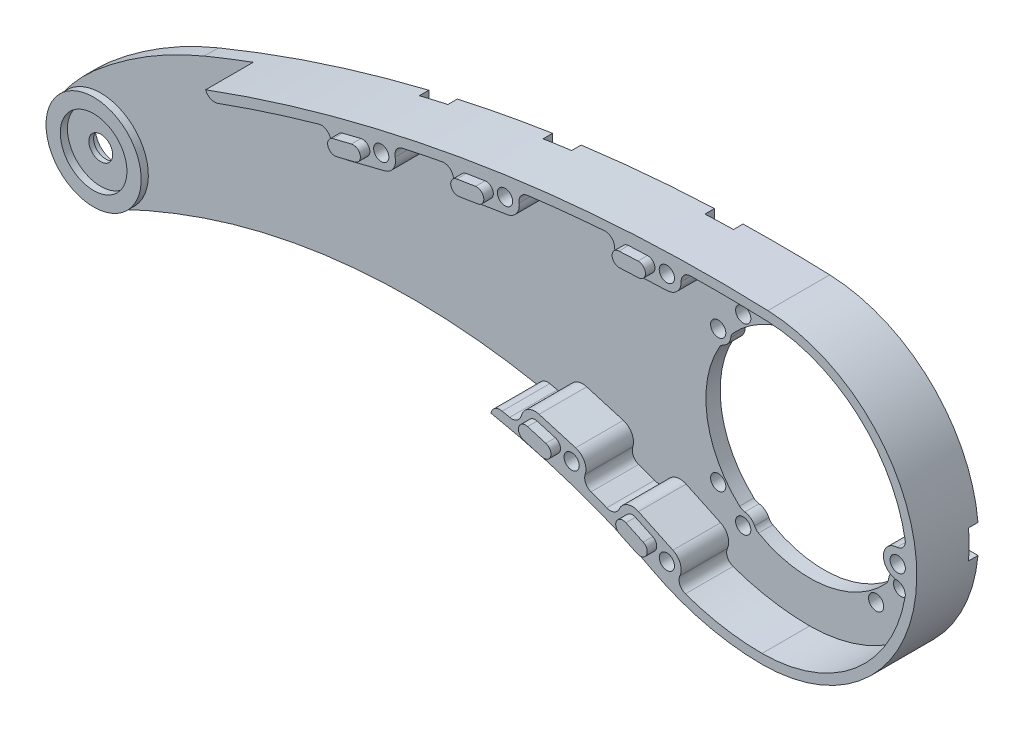
SolidWorks part; units mm, degrees
material "6061-T6 (SS)"
ref_plane "前视基准面" through (0, 0, 0) normal (0, 0, 1) x (1, 0, 0)
ref_plane "上视基准面" through (0, 0, 0) normal (0, 1, 0) x (1, 0, 0)
ref_plane "右视基准面" through (0, 0, 0) normal (1, 0, 0) x (0, 0, -1)
other "Configuration Table"
sketch "草图1" plane through (0, 0, 0) normal (0, 0, 1) x (1, 0, 0)
  line L0 (-74.3846, 0) -> (17.4339, 0) construction
  line L1 (0, 31.8895) -> (0, -25.7876) construction
  line L2 (0, 0) -> (19.2142, 13.9599) construction
  line L3 (0, 0) -> (13.9599, 19.2142) construction
  line L4 (0, 0) -> (-148.9161, -18) construction
  line L6 (0, 0) -> (-1.2281, 22.9672) construction
  line L8 (-1.2281, 22.9672) -> (-150.1441, 4.9672) construction
  line L9 (-150.1441, 4.9672) -> (-148.9161, -18) construction
  line L10 (-148.9161, -18) -> (-97.5528, -158.9319)
  line L12 (0, 0) -> (-103.1063, -167.9797) construction
  arc A116 (16.0762, 14.724) -> (-10.7394, 18.9712) centre (0, 0) ccw
  circle A117 centre (0, 0) radius 23.75 construction
  circle A118 centre (19.2142, 13.9599) radius 1.6
  circle A119 centre (13.9599, 19.2142) radius 1.6
  circle A120 centre (19.2142, -13.9599) radius 1.6
  circle A121 centre (13.9599, -19.2142) radius 1.6
  circle A122 centre (-13.9599, -19.2142) radius 1.6
  circle A123 centre (-19.2142, -13.9599) radius 1.6
  circle A124 centre (-19.2142, 13.9599) radius 1.6
  circle A125 centre (-13.9599, 19.2142) radius 1.6
  arc A126 (0, -32.5) -> (1.2171, 32.4772) centre (0, 0) ccw
  arc A127 (-157.1671, -12.3502) -> (-144.5702, -27.0063) centre (-148.9161, -18) ccw
  arc A134 (-28.3708, -24.2609) -> (-127.3793, -19.9637) centre (-83.3912, -149.2082) ccw
  arc A135 (-127.3793, -19.9637) -> (-144.5702, -27.0063) centre (-78.0965, -164.7651) ccw
  arc A136 (1.2171, 32.4772) -> (-127.1723, 9.5805) centre (-10.2849, -274.4361) ccw
  arc A138 (-23.6381, -26.5665) -> (-28.3708, -24.2609) centre (-55.9067, -86.7929) ccw
  arc A139 (0, -32.5) -> (-23.6381, -26.5665) centre (0, 17.5518) cw
  arc A140 (16.5853, 13.6255) -> (18.0838, 11.5631) centre (19.2142, 13.9599) ccw
  arc A141 (16.5853, 13.6255) -> (16.0762, 14.724) centre (14.6013, 13.3732) ccw
  arc A142 (18.0838, 11.5631) -> (18.9712, 10.7394) centre (17.2307, 9.7541) cw
  arc A143 (11.5631, -18.0838) -> (10.7394, -18.9712) centre (9.7541, -17.2307) cw
  arc A144 (13.6255, -16.5853) -> (11.5631, -18.0838) centre (13.9599, -19.2142) ccw
  arc A145 (13.6255, -16.5853) -> (14.724, -16.0762) centre (13.3732, -14.6013) ccw
  arc A146 (-18.0838, -11.5631) -> (-18.9712, -10.7394) centre (-17.2307, -9.7541) cw
  arc A147 (-16.5853, -13.6255) -> (-18.0838, -11.5631) centre (-19.2142, -13.9599) ccw
  arc A148 (-16.5853, -13.6255) -> (-16.0762, -14.724) centre (-14.6013, -13.3732) ccw
  arc A149 (-11.5631, 18.0838) -> (-10.7394, 18.9712) centre (-9.7541, 17.2307) cw
  arc A150 (-13.6255, 16.5853) -> (-11.5631, 18.0838) centre (-13.9599, 19.2142) ccw
  arc A151 (-13.6255, 16.5853) -> (-14.724, 16.0762) centre (-13.3732, 14.6013) ccw
  arc A152 (-16.0762, -14.724) -> (10.7394, -18.9712) centre (0, 0) ccw
  arc A153 (14.724, -16.0762) -> (18.9712, 10.7394) centre (0, 0) ccw
  arc A154 (-14.724, 16.0762) -> (-18.9712, -10.7394) centre (0, 0) ccw
  arc A155 (-127.1723, 9.5805) -> (-150.1438, -4.5112) centre (-94.9478, -68.7195) ccw
  arc A156 (-150.1438, -4.5112) -> (-157.1671, -12.3502) centre (-123.7132, -35.2574) ccw
  arc A157 (11.5631, 18.0838) -> (10.7394, 18.9712) centre (9.7541, 17.2307) ccw
  arc A158 (11.5631, 18.0838) -> (13.6255, 16.5853) centre (13.9599, 19.2142) ccw
  arc A159 (13.6255, 16.5853) -> (14.724, 16.0762) centre (13.3732, 14.6013) cw
  arc A160 (16.5853, -13.6255) -> (16.0762, -14.724) centre (14.6013, -13.3732) cw
  arc A161 (18.0838, -11.5631) -> (16.5853, -13.6255) centre (19.2142, -13.9599) ccw
  arc A162 (18.0838, -11.5631) -> (18.9712, -10.7394) centre (17.2307, -9.7541) ccw
  arc A163 (-13.6255, -16.5853) -> (-14.724, -16.0762) centre (-13.3732, -14.6013) cw
  arc A164 (-11.5631, -18.0838) -> (-13.6255, -16.5853) centre (-13.9599, -19.2142) ccw
  arc A165 (-11.5631, -18.0838) -> (-10.7394, -18.9712) centre (-9.7541, -17.2307) ccw
  arc A166 (-16.5853, 13.6255) -> (-16.0762, 14.724) centre (-14.6013, 13.3732) cw
  arc A167 (-18.0838, 11.5631) -> (-16.5853, 13.6255) centre (-19.2142, 13.9599) ccw
  arc A168 (-18.0838, 11.5631) -> (-18.9712, 10.7394) centre (-17.2307, 9.7541) ccw
  arc A169 (18.9712, 10.7394) -> (16.0762, 14.724) centre (0, 0) ccw
  arc A170 (-10.7394, 18.9712) -> (-14.724, 16.0762) centre (0, 0) ccw
  arc A171 (10.7394, -18.9712) -> (14.724, -16.0762) centre (0, 0) ccw
  arc A172 (-16.0762, -14.724) -> (-18.9712, -10.7394) centre (0, 0) cw
  point P27 (0, 0)
  point P73 (0, 0)
  point P83 (0, 0)
  point P105 (0, 0)
  dimension "D1" = 43.6
  dimension "D3" = 36
  dimension "D4" = 3.2
  dimension "D2" = 47.5
  dimension "D6" = 3.2
  dimension "D8" = 65
  dimension "D15" = 20
  dimension "D16" = 5.3
  dimension "D17" = 2
  dimension "D5" = 18
  dimension "D9" = 18
  dimension "D10" = 150
  dimension "D11" = 23
  dimension "D12" = 150
  dimension "D13" = 103.132
  dimension "D14" = 51.566
  dimension "D19" = 2
  dimension "D7" = 4
  dimension "D18" = 4
  dimension "D20" = 4
extrude "凸台-拉伸1" add sketch "草图1" along normal blind 3 contours A135 A134 A138 A126 A127 A125 A124 A123 A122 A121 A120 A119 A118 A116 | A168 A167 A166 A154 | A158 A159 A116 A157 | A162 A161 A160 A153 | A165 A164 A163 A152 region at (12.6444, 17.4035, 0) region at (17.4035, -12.6444, 0) region at (-17.4035, 12.6444, 0) region at (-12.6444, -17.4035, 0) region at (-60.0806, 1.6127, 0)
sketch "草图2" plane through (0, 0, 0) normal (0, 0, -1) x (-1, 0, 0)
  line L0 (-28.5, 0) -> (0, 0) construction
  line L2 (0, 0) -> (18.5599, 13.5842) construction
  line L3 (18.5599, 13.5842) -> (167.476, -4.4158) construction
  line L4 (167.476, -4.4158) -> (148.9161, -18) construction
  line L5 (148.9161, -18) -> (10.6983, -76.2738) construction
  line L7 (25.351, 15.2815) -> (162.3611, -1.2794) construction
  line L9 (24.751, 10.3176) -> (161.7611, -6.2433) construction
  line L11 (19.8643, 25.54) -> (27.8561, 25.1781)
  line L13 (18.7235, -21.0787) -> (25.9631, -17.6745)
  line L16 (53.5282, 22.5613) -> (61.4287, 21.3032)
  line L17 (79.2716, 17.6568) -> (87.0322, 15.7143)
  line L19 (116.7753, -9.6208) -> (124.5035, -11.6883)
  line L20 (39.1553, -12.6715) -> (46.8316, -10.4188)
  arc A111 (-1.1422, 30.4786) -> (-30.0624, 5.1483) centre (0, 0) ccw
  arc A112 (0, -30.5) -> (16.1065, -27.7202) centre (0, 17.5518) ccw
  arc A114 (110.6875, -13.3991) -> (53.0075, -14.0564) centre (83.3912, -149.2082) ccw
  arc A115 (128.6525, -18.2859) -> (127.8763, -18.0203) centre (78.0965, -164.7651) ccw
  arc A116 (144.5702, -27.0063) -> (157.1671, -12.3502) centre (148.9161, -18) ccw
  arc A118 (157.1671, -12.3502) -> (150.1438, -4.5112) centre (123.7132, -35.2574) ccw
  arc A119 (127.1723, 9.5805) -> (-1.2171, 32.4772) centre (10.2849, -274.4361) ccw
  arc A120 (-1.2171, 32.4772) -> (0, -32.5) centre (0, 0) ccw
  arc A121 (-1.0673, 28.48) -> (0, -28.5) centre (0, 0) ccw construction
  arc A122 (0, -32.5) -> (23.6381, -26.5665) centre (0, 17.5518) ccw
  arc A123 (28.3708, -24.2609) -> (23.6381, -26.5665) centre (55.9067, -86.7929) ccw
  arc A124 (127.3793, -19.9637) -> (28.3708, -24.2609) centre (83.3912, -149.2082) ccw
  arc A125 (144.5702, -27.0063) -> (127.3793, -19.9637) centre (78.0965, -164.7651) ccw
  arc A126 (144.5702, -27.0063) -> (157.1671, -12.3502) centre (148.9161, -18) ccw
  arc A128 (127.1723, 9.5805) -> (-1.2171, 32.4772) centre (10.2849, -274.4361) ccw
  arc A129 (-1.2171, 32.4772) -> (0, -32.5) centre (0, 0) ccw
  arc A130 (0, -32.5) -> (23.6381, -26.5665) centre (0, 17.5518) ccw
  arc A131 (28.3708, -24.2609) -> (23.6381, -26.5665) centre (55.9067, -86.7929) ccw
  arc A132 (127.3793, -19.9637) -> (28.3708, -24.2609) centre (83.3912, -149.2082) ccw
  arc A133 (144.5702, -27.0063) -> (127.3793, -19.9637) centre (78.0965, -164.7651) ccw
  arc A134 (0, -28.5) -> (21.749, -23.0407) centre (0, 17.5518) ccw construction
  arc A135 (26.7587, -20.6001) -> (21.749, -23.0407) centre (55.9067, -86.7929) ccw construction
  arc A136 (128.6681, -16.177) -> (26.7587, -20.6001) centre (83.3912, -149.2082) ccw construction
  arc A137 (146.3086, -23.4038) -> (128.6681, -16.177) centre (78.0965, -164.7651) ccw construction
  arc A138 (146.3086, -23.4038) -> (153.7238, -14.4104) centre (148.9161, -18) ccw construction
  arc A139 (153.7238, -14.4104) -> (126.0955, 5.6977) centre (120.8678, -30.5198) ccw construction
  arc A140 (126.0955, 5.6977) -> (-1.0673, 28.48) centre (10.2849, -274.4361) ccw construction
  arc A141 (-28.3421, -2.9958) -> (-28.3421, 2.9958) centre (-28.5, 0) ccw
  arc A142 (-28.3421, 2.9958) -> (-30.0624, 5.1483) centre (-28.2451, 4.837) cw
  arc A143 (-28.3421, -2.9958) -> (-30.0624, -5.1483) centre (-28.2451, -4.837) ccw
  arc A144 (-30.0624, -5.1483) -> (0, -30.5) centre (0, 0) ccw
  circle A145 centre (-28.5, 0) radius 1.6
  arc A146 (-1.1422, 30.4786) -> (0, -30.5) centre (0, 0) ccw construction
  circle A147 centre (18.5599, 13.5842) radius 7 construction
  circle A148 centre (167.476, -4.4158) radius 6 construction
  arc A149 (17.0011, 28.6182) -> (19.8643, 25.54) centre (20, 28.5369) ccw
  arc A150 (27.8561, 25.1781) -> (30.9858, 27.985) centre (27.9918, 28.175) ccw
  arc A151 (17.0011, 28.6182) -> (15.0491, 30.6555) centre (15.0181, 28.672) ccw
  arc A152 (30.9858, 27.985) -> (33.1139, 29.8374) centre (32.9655, 27.8593) cw
  arc A153 (15.0491, 30.6555) -> (-1.1422, 30.4786) centre (10.2849, -274.4361) ccw
  circle A154 centre (20, 28.5369) radius 1.6
  arc A155 (126.6313, 7.6402) -> (-1.1422, 30.4786) centre (10.2849, -274.4361) ccw construction
  arc A156 (17.2617, -25.019) -> (18.7235, -21.0787) centre (20, -23.7935) cw
  arc A157 (25.9631, -17.6745) -> (30.0023, -19.2201) centre (27.2396, -20.3894) cw
  circle A158 centre (20, -23.7935) radius 1.6
  arc A159 (17.2617, -25.019) -> (16.1065, -27.7202) centre (15.4362, -25.8359) cw
  arc A160 (30.0023, -19.2201) -> (32.6241, -20.3211) centre (31.8778, -18.4263) ccw
  circle A161 centre (54, 25.524) radius 1.6
  arc A162 (27.5648, -22.4305) -> (22.6935, -24.8036) centre (55.9067, -86.7929) ccw construction
  arc A163 (0, -30.5) -> (22.6935, -24.8036) centre (0, 17.5518) ccw construction
  arc A164 (128.0237, -18.0703) -> (27.5648, -22.4305) centre (83.3912, -149.2082) ccw construction
  arc A165 (51.0293, 25.9419) -> (53.5282, 22.5613) centre (54, 25.524) ccw
  arc A166 (61.4287, 21.3032) -> (64.8541, 23.7404) centre (61.9005, 24.2659) ccw
  arc A167 (51.0293, 25.9419) -> (49.3187, 28.1856) centre (49.0649, 26.2183) ccw
  arc A168 (64.8541, 23.7404) -> (67.177, 25.3419) centre (66.8071, 23.393) cw
  arc A169 (49.3187, 28.1856) -> (33.1139, 29.8374) centre (10.2849, -274.4361) ccw
  circle A170 centre (80, 20.567) radius 1.6
  arc A171 (77.077, 21.2425) -> (79.2716, 17.6568) centre (80, 20.567) ccw
  arc A172 (87.0322, 15.7143) -> (90.6571, 17.8435) centre (87.7606, 18.6246) ccw
  arc A173 (77.077, 21.2425) -> (75.5687, 23.6269) centre (75.1443, 21.6892) ccw
  arc A175 (75.5687, 23.6269) -> (67.177, 25.3419) centre (10.2849, -274.4361) ccw
  circle A176 centre (40, -15.5501) radius 1.6
  circle A177 centre (116, -12.5189) radius 1.6
  arc A178 (37.1566, -16.5068) -> (39.1553, -12.6715) centre (40, -15.5501) cw
  arc A180 (37.1566, -16.5068) -> (35.9243, -19.0695) centre (35.2265, -17.1563) cw
  arc A182 (35.9243, -19.0695) -> (32.6241, -20.3211) centre (83.3912, -149.2082) ccw
  arc A183 (113.0746, -11.854) -> (116.7753, -9.6208) centre (116, -12.5189) cw
  arc A184 (124.5035, -11.6883) -> (126.5902, -15.4859) centre (123.7282, -14.5864) cw
  arc A185 (113.0746, -11.854) -> (110.6875, -13.3991) centre (111.0888, -11.4026) cw
  arc A186 (126.5902, -15.4859) -> (127.8763, -18.0203) centre (128.5292, -16.0954) ccw
  arc A187 (128.6525, -18.2859) -> (129.8863, -20.8413) centre (128, -20.1764) cw
  arc A188 (145.4394, -25.205) -> (128.0237, -18.0703) centre (78.0965, -164.7651) ccw construction
  arc A189 (144.5702, -27.0063) -> (127.3793, -19.9637) centre (78.0965, -164.7651) ccw construction
  arc A190 (145.4394, -25.205) -> (155.4422, -13.3729) centre (148.9161, -18) ccw construction
  arc A191 (75.5687, 23.6269) -> (93.1109, 19.2362) centre (10.2849, -274.4361) cw construction
  arc A192 (90.6571, 17.8435) -> (93.1109, 19.2362) centre (92.5724, 17.327) cw
  arc A193 (155.4422, -13.3729) -> (126.6313, 7.6402) centre (120.8678, -30.5198) ccw construction
  arc A194 (15.0491, 30.6555) -> (33.1139, 29.8374) centre (10.2849, -274.4361) cw construction
  arc A195 (49.3187, 28.1856) -> (67.177, 25.3419) centre (10.2849, -274.4361) cw construction
  arc A196 (93.1109, 19.2362) -> (114.3181, 12.4099) centre (10.2849, -274.4361) cw
  arc A197 (114.3181, 12.4099) -> (116.8779, 13.6021) centre (115, 14.2901) ccw
  arc A198 (46.8316, -10.4188) -> (50.5858, -12.566) centre (47.6763, -13.2974) cw
  arc A199 (50.5858, -12.566) -> (53.0075, -14.0564) centre (52.5608, -12.0695) ccw
  arc A200 (54.5841, -13.7116) -> (56.9593, -15.2663) centre (55, -15.6678) cw
  arc A207 (157.1671, -12.3502) -> (127.1723, 9.5805) centre (120.8678, -30.5198) ccw construction
  arc A208 (157.1671, -12.3502) -> (150.1438, -4.5112) centre (123.7132, -35.2574) ccw
  arc A209 (150.1438, -4.5112) -> (127.1723, 9.5805) centre (94.9478, -68.7195) ccw
  arc A210 (150.1438, -4.5112) -> (127.1723, 9.5805) centre (94.9478, -68.7195) ccw
  point P113 (16.5105, -418.9921)
  arc M20 (127.1723, 9.5805) -> (-1.2171, 32.4772) centre (10.2849, -274.4361) ccw
  arc M21 (-1.2171, 32.4772) -> (0, -32.5) centre (0, 0) ccw
  arc M22 (0, -32.5) -> (23.6381, -26.5665) centre (0, 17.5518) ccw
  arc M23 (23.6381, -26.5665) -> (28.3708, -24.2609) centre (55.9067, -86.7929) cw
  arc M24 (28.3708, -24.2609) -> (127.3793, -19.9637) centre (83.3912, -149.2082) cw
  arc M25 (127.3793, -19.9637) -> (144.5702, -27.0063) centre (78.0965, -164.7651) cw
  dimension "D7" = 150
  dimension "D9" = 14
  dimension "D11" = 12
  dimension "D12" = 150
  dimension "D13" = 8
  dimension "D10" = 2.5
  dimension "D8" = 166.66
  dimension "D14" = 20
  dimension "D15" = 8
  dimension "D16" = 8
  dimension "D17" = 8
  dimension "D18" = 54
  dimension "D19" = 80
  dimension "D20" = 8
  dimension "D21" = 40
  dimension "D22" = 116
  dimension "D23" = 8
  dimension "D6" = 23
  dimension "D25" = 128
  dimension "D26" = 2
  dimension "D27" = 115
  dimension "D28" = 20
  dimension "D4" = 6
  dimension "D5" = 3.2
  dimension "D24" = 2
  dimension "D29" = 2
  dimension "D1" = 0
  dimension "D2" = 2
  dimension "D3" = 2
  dimension "D30" = 55
extrude "凸台-拉伸2" add sketch "草图2" along normal blind 10 contours M20 M21 M22 M23 M24 M25 region at (-17.9227, 26.6047, 0)
sketch "草图4" plane through (0, 0, -10) normal (0, 0, -1) x (-1, 0, 0)
  line L0 (20, 28.5369) -> (27.9918, 28.175) construction
  line L3 (61.9005, 24.2659) -> (54, 25.524) construction
  line L8 (80, 20.567) -> (87.7606, 18.6246) construction
  line L9 (20, -23.7935) -> (27.2396, -20.3894) construction
  line L10 (40, -15.5501) -> (47.6763, -13.2974) construction
  line L11 (116, -12.5189) -> (123.7282, -14.5864) construction
  line L12 (27.2396, -20.3894) -> (23.6198, -22.0915) construction
  line L15 (27.8779, -21.7468) -> (24.2581, -23.4489)
  line L24 (26.6013, -19.032) -> (22.9815, -20.734)
  line L27 (27.9918, 28.175) -> (23.9959, 28.356) construction
  line L30 (27.924, 26.6766) -> (23.9281, 26.8575)
  line L33 (28.0597, 29.6735) -> (24.0638, 29.8545)
  line L36 (61.9005, 24.2659) -> (57.9502, 24.8949) construction
  line L39 (87.7606, 18.6246) -> (83.8803, 19.5958) construction
  line L40 (87.3964, 17.1695) -> (83.5161, 18.1407)
  line L41 (88.1248, 20.0797) -> (84.2445, 21.0509)
  line L42 (123.7282, -14.5864) -> (119.8641, -13.5526) construction
  line L43 (123.3406, -16.0354) -> (119.4765, -15.0017)
  line L44 (124.1159, -13.1373) -> (120.2518, -12.1036)
  line L45 (47.6763, -13.2974) -> (43.8382, -14.4238) construction
  line L46 (48.0987, -14.7367) -> (44.2605, -15.8631)
  line L47 (47.2539, -11.8581) -> (43.4158, -12.9845)
  line L48 (61.6646, 22.7845) -> (57.7143, 23.4136)
  line L49 (62.1363, 25.7472) -> (58.1861, 26.3763)
  arc A24 (27.8779, -21.7468) -> (26.6013, -19.032) centre (27.2396, -20.3894) ccw
  arc A25 (22.9815, -20.734) -> (24.2581, -23.4489) centre (23.6198, -22.0915) ccw
  arc A26 (27.924, 26.6766) -> (28.0597, 29.6735) centre (27.9918, 28.175) ccw
  arc A27 (24.0638, 29.8545) -> (23.9281, 26.8575) centre (23.9959, 28.356) ccw
  arc A30 (87.3964, 17.1695) -> (88.1248, 20.0797) centre (87.7606, 18.6246) ccw
  arc A31 (84.2445, 21.0509) -> (83.5161, 18.1407) centre (83.8803, 19.5958) ccw
  arc A32 (123.3406, -16.0354) -> (124.1159, -13.1373) centre (123.7282, -14.5864) ccw
  arc A33 (120.2518, -12.1036) -> (119.4765, -15.0017) centre (119.8641, -13.5526) ccw
  arc A34 (48.0987, -14.7367) -> (47.2539, -11.8581) centre (47.6763, -13.2974) ccw
  arc A35 (43.4158, -12.9845) -> (44.2605, -15.8631) centre (43.8382, -14.4238) ccw
  arc A36 (61.6646, 22.7845) -> (62.1363, 25.7472) centre (61.9005, 24.2659) ccw
  arc A37 (58.1861, 26.3763) -> (57.7143, 23.4136) centre (57.9502, 24.8949) ccw
  point P12 (25.4297, -21.2404)
  point P18 (25.9939, 28.2655)
  point P24 (59.9253, 24.5804)
  point P30 (85.8204, 19.1102)
  point P36 (121.7962, -14.0695)
  point P42 (45.7572, -13.8606)
  dimension "D2" = 1.5
  dimension "D1" = 4
extrude "凸台-拉伸3" add sketch "草图4" along normal blind 2 contours L33 A27 L30 A26 | L49 A37 L48 A36 | A30 L41 A31 L40 | A34 L47 A35 L46 | A24 L24 A25 L15
sketch "草图5" plane through (0, 0, -10) normal (0, 0, -1) x (-1, 0, 0)
  circle A2 centre (-28.5, 0) radius 1.6 construction
  circle A4 centre (-28.5, 0) radius 1.6
  circle A6 centre (54, 25.524) radius 1.6 construction
  circle A8 centre (80, 20.567) radius 1.6 construction
  circle A12 centre (40, -15.5501) radius 1.6 construction
  circle A14 centre (20, -23.7935) radius 1.6 construction
  circle A27 centre (20, 28.5369) radius 1.6 construction
  circle A28 centre (54, 25.524) radius 1.6
  circle A29 centre (80, 20.567) radius 1.6
  circle A31 centre (40, -15.5501) radius 1.6
  circle A32 centre (20, -23.7935) radius 1.6
  circle A33 centre (20, 28.5369) radius 1.6
extrude "切除-拉伸1" cut sketch "草图5" against normal up to next
sketch "草图10" plane through (0, 0, 0) normal (0, 0, -1) x (-1, 0, 0)
  circle A0 centre (148.9161, -18) radius 2.5
  dimension "D1" = 5
extrude "切除-拉伸4" cut sketch "草图10" against normal up to next
sketch "草图11" plane through (0, 0, 3) normal (0, 0, 1) x (1, 0, 0)
  circle A0 centre (-148.9161, -18) radius 4.15
  dimension "D1" = 8.3
extrude "切除-拉伸5" cut sketch "草图11" against normal blind 2
sketch "草图13" plane through (0, 0, 3) normal (0, 0, 1) x (1, 0, 0)
  line L0 (-83, 20.567) -> (-83, 23.9606)
  line L1 (-77, 20.567) -> (-77, 25.3591)
  line L2 (-57, 25.524) -> (-57, 29.1191)
  line L3 (-51, 25.524) -> (-51, 29.982)
  line L4 (-23, 28.5369) -> (-23, 32.4293)
  line L5 (-17, 28.5369) -> (-17, 32.6192)
  line L8 (-43, -15.5501) -> (-43, -18.7949)
  line L9 (-37, -15.5501) -> (-37, -20.8067)
  line L10 (-23, -23.7935) -> (-23, -26.9025)
  line L11 (-17, -23.7935) -> (-17, -29.5246)
  line L12 (28.5, 3) -> (32.3612, 3)
  line L13 (28.5, -3) -> (32.3612, -3)
  line L14 (28.5, 3) -> (28.5, -3) construction
  arc A0 (-83, 20.567) -> (-77, 20.567) centre (-80, 20.567) ccw
  arc A1 (-57, 25.524) -> (-51, 25.524) centre (-54, 25.524) ccw
  arc A2 (-23, 28.5369) -> (-17, 28.5369) centre (-20, 28.5369) ccw
  arc A3 (28.5, 3) -> (28.5, -3) centre (28.5, 0) ccw
  arc A5 (-37, -15.5501) -> (-43, -15.5501) centre (-40, -15.5501) ccw
  arc A7 (-23.6381, -26.5665) -> (0, -32.5) centre (0, 17.5518) ccw construction
  arc A8 (1.2171, 32.4772) -> (-127.1723, 9.5805) centre (-10.2849, -274.4361) ccw construction
  arc A9 (-28.3708, -24.2609) -> (-127.3793, -19.9637) centre (-83.3912, -149.2082) ccw construction
  arc A10 (-23.6381, -26.5665) -> (0, -32.5) centre (0, 17.5518) ccw
  arc A11 (-23.6381, -26.5665) -> (-28.3708, -24.2609) centre (-55.9067, -86.7929) ccw construction
  arc A12 (0, -32.5) -> (1.2171, 32.4772) centre (0, 0) ccw construction
  arc A13 (1.2171, 32.4772) -> (-127.1723, 9.5805) centre (-10.2849, -274.4361) ccw
  arc A15 (0, -32.5) -> (1.2171, 32.4772) centre (0, 0) ccw
  arc A16 (-23.6381, -26.5665) -> (-28.3708, -24.2609) centre (-55.9067, -86.7929) ccw
  arc A18 (-17, -23.7935) -> (-23, -23.7935) centre (-20, -23.7935) ccw
  arc A19 (-28.3708, -24.2609) -> (-127.3793, -19.9637) centre (-83.3912, -149.2082) ccw
  circle M9 centre (28.5, 0) radius 1.6
  circle M10 centre (-54, 25.524) radius 1.6
  circle M11 centre (-80, 20.567) radius 1.6
  circle M13 centre (-40, -15.5501) radius 1.6
  circle M14 centre (-20, -23.7935) radius 1.6
  circle M15 centre (-20, 28.5369) radius 1.6
  arc M17 (-127.3793, -19.9637) -> (-28.3708, -24.2609) centre (-83.3912, -149.2082) cw
  arc M19 (-23.6381, -26.5665) -> (0, -32.5) centre (0, 17.5518) ccw
  arc M20 (0, -32.5) -> (1.2171, 32.4772) centre (0, 0) ccw
  arc M21 (1.2171, 32.4772) -> (-127.1723, 9.5805) centre (-10.2849, -274.4361) ccw
  dimension "D1" = 6
  dimension "D2" = 6
  dimension "D3" = 3
extrude "切除-拉伸6" cut sketch "草图13" against normal blind 2 contours L9 A5 L8 M17 M13 | L11 A18 L10 M19 M14 | L12 L14 L13 M9 M20 | L14 A3 M9 | L4 A2 L5 M21 M15 | L2 A1 L3 M21 M10 | L0 A0 L1 M21 M11 region at (-39.9559, -19.6692, 3) region at (-20.0005, -28.2147, 3) region at (30.7421, 0, 3) region at (-19.9975, 32.4462, 3) region at (-53.9885, 29.4706, 3) region at (-82.9017, 22.2638, 3) region at (28.4329, 2.3, 3)
sketch "草图14" plane through (0, 0, 0) normal (0, 0, -1) x (-1, 0, 0)
  circle A0 centre (148.9161, -18) radius 10
  circle A1 centre (148.9161, -18) radius 7
  dimension "D1" = 14
  dimension "D2" = 20
extrude "凸台-拉伸4" add sketch "草图14" along normal blind 1.5
mirror "镜向1" about plane through (0, 0, 3) normal (0, 0, 1) of bodies 139
sketch "草图15" plane through (0, 0, -12) normal (0, 0, -1) x (-1, 0, 0)
  line L1 (-35.6451, 57.1538) -> (167.8467, 57.1538)
  line L2 (-35.6451, 57.1538) -> (-35.6451, -44.9911)
  line L3 (-35.6451, -44.9911) -> (167.8467, -44.9911)
  line L4 (167.8467, 57.1538) -> (167.8467, -44.9911)
extrude "切除-拉伸7" cut sketch "草图15" against normal blind 15
